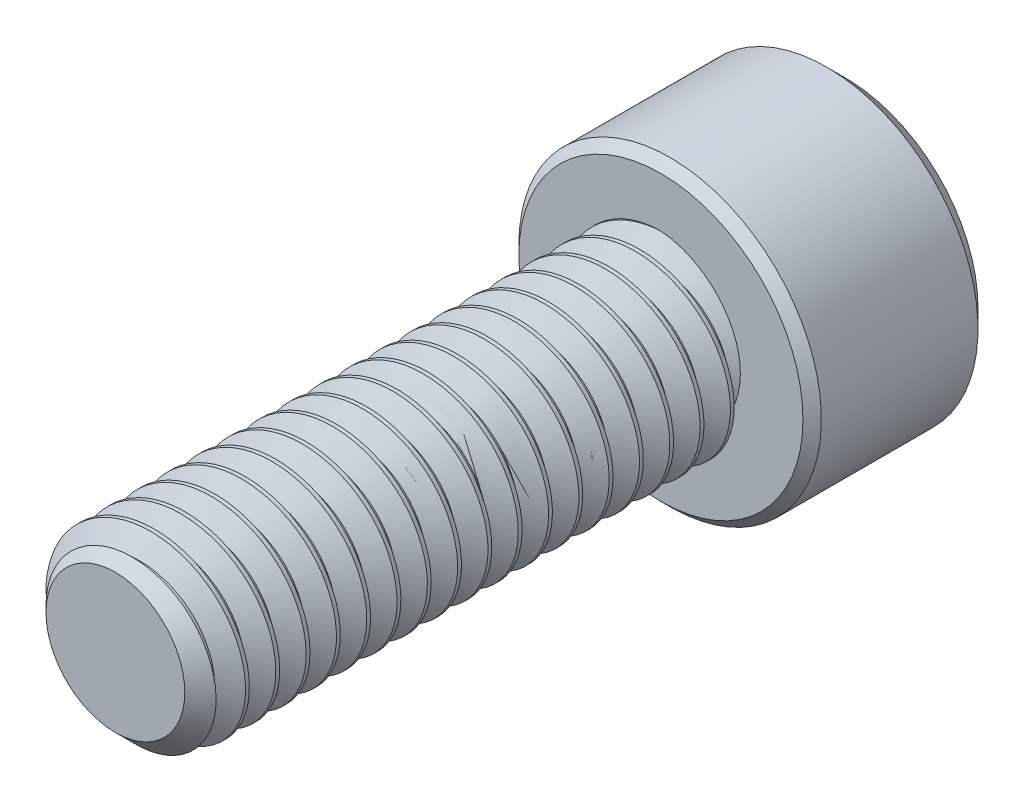
SolidWorks part; units mm, degrees
ref_plane "Front Plane" through (0, 0, 0) normal (0, 0, 1) x (1, 0, 0)
ref_plane "Top Plane" through (0, 0, 0) normal (0, 1, 0) x (1, 0, 0)
ref_plane "Right Plane" through (0, 0, 0) normal (1, 0, 0) x (0, 0, -1)
sketch "Sketch1" plane through (0, 0, 0) normal (0, 0, 1) x (1, 0, 0)
  line L0 (0, 2.413) -> (0, -2.413) construction
  circle A0 centre (0, 0) radius 2.413
  dimension "OD" = 4.826
extrude "Extrude1" add sketch "Sketch1" against normal blind 14.2875
sketch "Sketch2" plane through (0, 0, 0) normal (0, 0, 1) x (1, 0, 0)
  circle A0 centre (0, 0) radius 2.413 construction
  circle A1 centre (0, 0) radius 2.413
curve "Helix/Spiral1" pitch 0.7937 height 15.0812 turns 19 parameters "pitch"=0.7937
chamfer "Chamfer3" distance 0.5953 angle 45 1 edges at (2.413, 0, 0)
sketch "Sketch3" plane through (0, 0, 0) normal (1, 0, 0) x (0, 0, -1)
  line L0 (-0.6945, 2.413) -> (-0.3969, 1.8974)
  line L1 (-0.3969, 1.8974) -> (-0.2977, 1.8974)
  line L2 (-0.2977, 1.8974) -> (0, 2.413)
  line L3 (-0.6945, 2.413) -> (0, 2.413)
  line L4 (-0.3473, 2.413) -> (-0.3473, 1.8974) construction
  line L5 (-0.5457, 2.1552) -> (-0.1488, 2.1552) construction
  line L6 (0, 2.413) -> (0, -2.413) construction
  dimension "D1" = 0.0992
  dimension "D2" = 0.3969
  dimension "D3" = 60
sweep "Cut-Sweep1" cut profiles "Sketch3" path "Helix/Spiral1"
sketch "Sketch6" plane through (0, 0, -14.2875) normal (0, 0, -1) x (-1, 0, 0)
  circle A0 centre (0, 0) radius 3.9624
  dimension "head dia" = 7.9248
extrude "Extrude2" add sketch "Sketch6" along normal blind 4.826
sketch "Sketch7" plane through (0, 0, -19.1135) normal (0, 0, -1) x (-1, 0, 0)
  line L1 (0, 2.2914) -> (-1.9844, 1.1457)
  line L2 (-1.9844, 1.1457) -> (-1.9844, -1.1457)
  line L3 (-1.9844, -1.1457) -> (0, -2.2914)
  line L4 (0, -2.2914) -> (1.9844, -1.1457)
  line L5 (1.9844, -1.1457) -> (1.9844, 1.1457)
  line L6 (1.9844, 1.1457) -> (0, 2.2914)
  circle A0 centre (0, 0) radius 1.9844 construction
  dimension "hex dia" = 3.9688
extrude "Cut-Extrude1" cut sketch "Sketch7" against normal blind 2.9766
sketch "Sketch8" plane through (0, 0, -19.1135) normal (0, 0, -1) x (-1, 0, 0)
  circle A0 centre (0, 0) radius 2.2914
extrude "Cut-Extrude2" cut sketch "Sketch8" against normal blind 0.4826 draft 45
chamfer "Chamfer1" distance 0.4826 angle 45 1 edges at (-3.9624, 0, -19.1135)
chamfer "Chamfer2" distance 0.2413 angle 45 1 edges at (-3.9624, 0, -14.2875)
sketch "Sketch9" plane through (0, 0, 0) normal (1, 0, 0) x (0, 0, -1)
  line L0 (0, 2.413) -> (0, -2.413) construction
  line L1 (4.3656, 2.413) -> (4.3656, -2.413) construction
  line L2 (14.2875, 3.9624) -> (14.2875, -3.9624) construction
  line L3 (19.1135, 3.9624) -> (19.1135, -3.9624) construction
  line L4 (19.1135, 0) -> (0, 0) construction
  dimension "D1" = 4.3656
  dimension "D2" = 4.826
  dimension "D3" = 7.9248
  dimension "D4" = 14.2875
equation "\"D3@Helix/Spiral1\" = \"screw length@Extrude1\"+\"pitch@Helix/Spiral1\""
equation "\"D1@Sketch3\" = \"pitch@Helix/Spiral1\"*.125"
equation "\"D2@Sketch3\" = \"pitch@Helix/Spiral1\"*.5"
equation "\"D1@Cut-Extrude1\" = \"hex dia@Sketch7\"*.75"
equation "\"D1@Chamfer1\" = \"head depth@Extrude2\"/10"
equation "\"D1@Sketch9\" = \"pitch@Helix/Spiral1\"*5.5"
equation "\"D1@Chamfer2\" = \"D1@Chamfer1\"/2"
equation "\"D1@Cut-Extrude2\" = \"D1@Chamfer2\"*2"
equation "\"D1@Chamfer3\" = \"pitch@Helix/Spiral1\"*.750"
equation "\"D2@Sketch9\" = \"head depth@Extrude2\""
equation "\"D3@Sketch9\" = \"head dia@Sketch6\""
equation "\"D4@Sketch9\" = \"screw length@Extrude1\""
